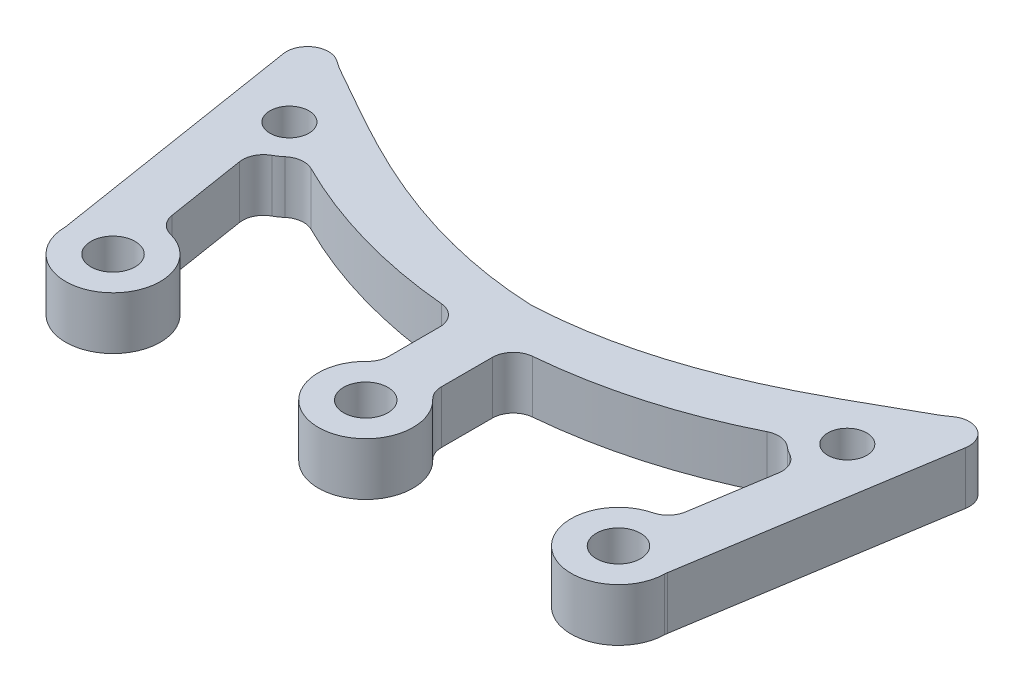
SolidWorks part; units mm, degrees
ref_plane "Front" through (0, 0, 0) normal (0, 0, 1) x (1, 0, 0)
ref_plane "Top" through (0, 0, 0) normal (0, 1, 0) x (1, 0, 0)
ref_plane "Right" through (0, 0, 0) normal (1, 0, 0) x (0, 0, -1)
sketch "Sketch1" plane through (0, 0, 0) normal (0, 1, 0) x (1, 0, 0)
  line L23 (31.5866, 14.3296) -> (31.5866, -49985.6704) construction
  line L28 (64.7036, 22.1539) -> (60.0866, -6.9436)
  line L31 (-1.5304, 22.1539) -> (3.0866, -6.9436)
  line L34 (29.0875, -3.2014) -> (29.0875, 4.446)
  line L36 (7.4362, -2.4462) -> (5.7303, 8.3045)
  line L37 (55.737, -2.4462) -> (57.4428, 8.3045)
  line L38 (34.0857, -3.2014) -> (34.0857, 4.446)
  circle A13 centre (7.5866, -6.9436) radius 2.1
  circle A18 centre (55.5866, -6.9436) radius 2.1
  circle A20 centre (31.5866, -6.9436) radius 2.1
  arc A23 (3.0866, -6.9436) -> (7.4362, -2.4462) centre (7.5866, -6.9436) ccw
  arc A25 (29.0875, -3.2014) -> (34.0857, -3.2014) centre (31.5866, -6.9436) ccw
  arc A27 (60.0866, -6.9436) -> (55.737, -2.4462) centre (55.5866, -6.9436) cw
  arc A29 (34.0857, 4.446) -> (54.6059, 10.223) centre (31.5866, 52.6559) ccw
  circle A30 centre (5.0966, 12.2985) radius 1.85
  circle A31 centre (58.0766, 12.2985) radius 1.85
  arc A32 (54.6059, 10.223) -> (57.4428, 8.3045) centre (58.0766, 12.2985) ccw
  arc A33 (5.7303, 8.3045) -> (8.5673, 10.223) centre (5.0966, 12.2985) ccw
  arc A34 (8.5673, 10.223) -> (29.0875, 4.446) centre (31.5866, 52.6559) ccw
  spline S0 degree 3 poles (3.0866, 19.0668) (6.2146, 17.3206) (15.2897, 11.954) (24.9915, 9.0119) (31.5866, 8.7238) knots 0.224842 0.224842 0.224842 0.224842 0.497996 1 1 1 1
  spline S1 degree 3 poles (60.0866, 19.0668) (56.9586, 17.3206) (47.8835, 11.954) (38.1817, 9.0119) (31.5866, 8.7238) knots 0.224842 0.224842 0.224842 0.224842 0.497996 1 1 1 1
  spline S2 degree 1 poles (3.0866, 19.0668) (-1.5304, 22.1539) knots 0 0 1 1
  spline S3 degree 1 poles (60.0866, 19.0668) (64.7036, 22.1539) knots 0 0 1 1
  dimension "D2" = 180
extrude "Boss-Extrude1" add sketch "Sketch1" along normal blind 5
fillet "Fillet1" radius 2 17 edges at (64.7036, 2.5, -22.1539) (60.0866, 2.5, 6.9436) (55.737, 2.5, 2.4462) (57.4428, 2.5, -8.3045) (54.6059, 2.5, -10.223) (34.0857, 2.5, -4.446) (34.0857, 2.5, 3.2014) (29.0875, 2.5, 3.2014) (29.0875, 2.5, -4.446) (5.7303, 2.5, -8.3045) (7.4362, 2.5, 2.4462) (3.0866, 2.5, 6.9436) (-1.5304, 2.5, -22.1539) (3.0866, 2.5, -19.0668) (31.5866, 2.5, -8.7238) (60.0866, 2.5, -19.0668) (8.5673, 2.5, -10.223)
